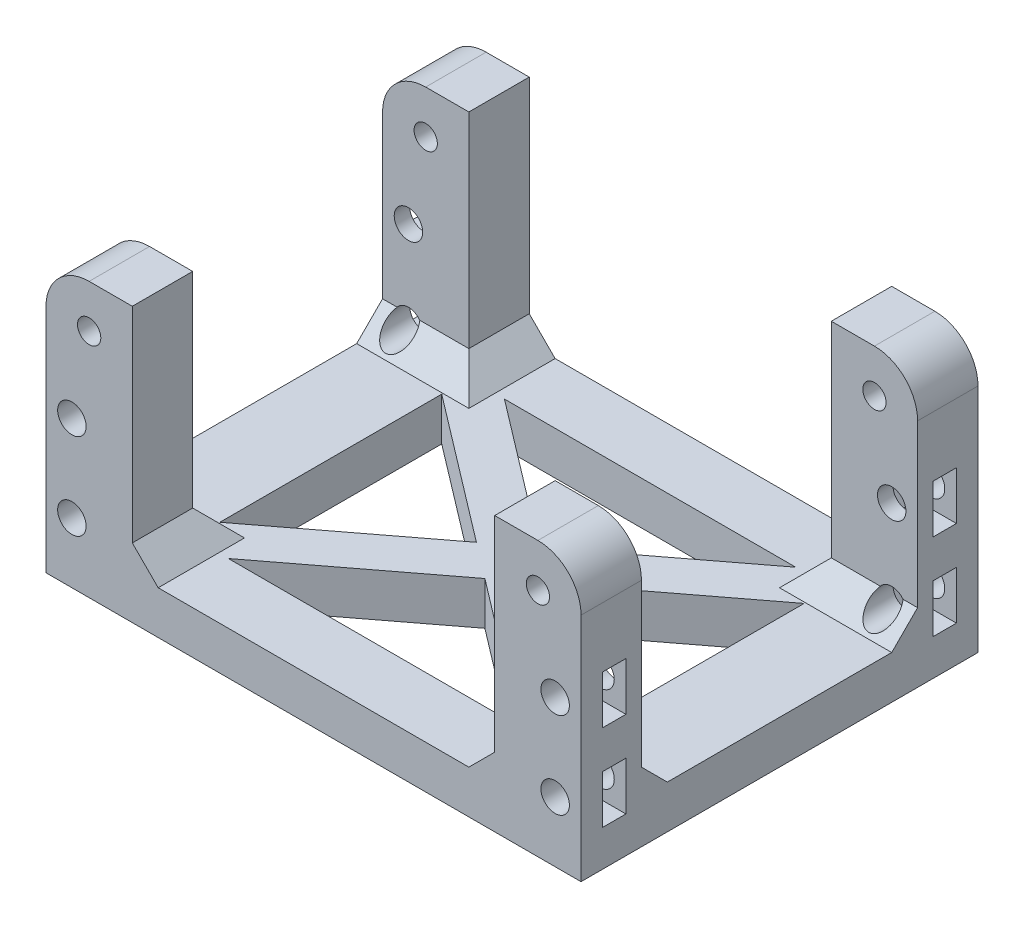
SolidWorks part; units mm, degrees
ref_plane "前视基准面" through (0, 0, 0) normal (0, 0, 1) x (1, 0, 0)
ref_plane "上视基准面" through (0, 0, 0) normal (0, 1, 0) x (1, 0, 0)
ref_plane "右视基准面" through (0, 0, 0) normal (1, 0, 0) x (0, 0, -1)
sketch "草图1" plane through (0, 0, 0) normal (0, 1, 0) x (1, 0, 0)
  line L1 (-31, -23) -> (31, -23)
  line L2 (-31, -23) -> (-31, 23)
  line L3 (-31, 23) -> (31, 23)
  line L4 (31, -23) -> (31, 23)
  line L5 (-31, -23) -> (31, 23) construction
  line L6 (-31, 23) -> (31, -23) construction
  point P0 (0, 0)
  dimension "D1" = 62
  dimension "D2" = 46
extrude "凸台-拉伸1" add sketch "草图1" along normal blind 5
sketch "草图2" plane through (0, 0, 23) normal (0, 0, 1) x (1, 0, 0)
  line L1 (-31, 5) -> (-21, 5)
  line L2 (-31, 5) -> (-31, 22)
  line L3 (-31, 22) -> (-21, 22)
  line L4 (-21, 5) -> (-21, 22)
  line L5 (31, 5) -> (21, 5)
  line L6 (31, 5) -> (31, 22)
  line L7 (31, 22) -> (21, 22)
  line L8 (21, 5) -> (21, 22)
  dimension "D1" = 17
  dimension "D2" = 10
extrude "凸台-拉伸2" add sketch "草图2" against normal blind 7
sketch "草图3" plane through (0, 0, 23) normal (0, 0, 1) x (1, 0, 0)
  line L0 (-21, 22) -> (21, 22) construction
  line L1 (0, 22) -> (0, 12) construction
  line L2 (-28, 7) -> (28, 7) construction
  line L3 (-28, 7) -> (-28, 17) construction
  line L4 (-28, 17) -> (28, 17) construction
  line L5 (28, 7) -> (28, 17) construction
  line L6 (-28, 7) -> (28, 17) construction
  line L7 (-28, 17) -> (28, 7) construction
  circle A0 centre (-28, 17) radius 1.65
  circle A1 centre (-28, 7) radius 1.65
  circle A2 centre (28, 7) radius 1.65
  circle A3 centre (28, 17) radius 1.65
  point P4 (0, 12)
  dimension "D3" = 3.3
  dimension "D1" = 10
  dimension "D2" = 56
  dimension "D4" = 10
extrude "切除-拉伸1" cut sketch "草图3" against normal blind 12
sketch "草图7" plane through (0, 22, 0) normal (0, 1, 0) x (1, 0, 0)
  line L1 (-31, -23) -> (-21, -23)
  line L2 (-31, -23) -> (-31, -16)
  line L3 (-31, -16) -> (-21, -16)
  line L4 (-21, -23) -> (-21, -16)
  line L5 (21, -23) -> (31, -23)
  line L6 (21, -23) -> (21, -16)
  line L7 (21, -16) -> (31, -16)
  line L8 (31, -23) -> (31, -16)
extrude "凸台-拉伸4" add sketch "草图7" along normal blind 9.75
sketch "草图8" plane through (0, 0, 23) normal (0, 0, 1) x (1, 0, 0)
  line L0 (-26, 31.75) -> (-26, 26.75) construction
  line L1 (-31, 31.75) -> (-21, 31.75) construction
  line L2 (26, 31.75) -> (26, 26.75) construction
  line L3 (21, 31.75) -> (31, 31.75) construction
  line L4 (-26, 26.75) -> (26, 26.75) construction
  circle A0 centre (-26, 26.75) radius 1.35
  circle A1 centre (26, 26.75) radius 1.35
  dimension "D2" = 2.7
  dimension "D1" = 5
extrude "切除-拉伸4" cut sketch "草图8" against normal up to next
ref_plane "基准面1" through (0, 0, 20.5) normal (0, 0, 1) x (1, 0, 0)
sketch "草图4" plane through (0, 0, 20.5) normal (0, 0, 1) x (1, 0, 0)
  line L0 (-29.6166, 19.8) -> (-31.2332, 19.8)
  line L1 (-24.7668, 17) -> (-26.3834, 19.8)
  line L2 (-26.3834, 19.8) -> (-29.6166, 19.8)
  line L3 (-29.6166, 19.8) -> (-31.2332, 17) construction
  line L4 (-31.2332, 17) -> (-29.6166, 14.2) construction
  line L5 (-29.6166, 14.2) -> (-26.3834, 14.2)
  line L6 (-26.3834, 14.2) -> (-24.7668, 17)
  line L7 (-24.7668, 7) -> (-26.3834, 9.8)
  line L8 (-26.3834, 9.8) -> (-29.6166, 9.8)
  line L9 (-29.6166, 9.8) -> (-31.2332, 7) construction
  line L10 (-31.2332, 7) -> (-29.6166, 4.2) construction
  line L11 (-29.6166, 4.2) -> (-26.3834, 4.2)
  line L12 (-26.3834, 4.2) -> (-24.7668, 7)
  line L13 (24.7668, 17) -> (26.3834, 14.2)
  line L14 (26.3834, 14.2) -> (29.6166, 14.2)
  line L15 (29.6166, 14.2) -> (31.2332, 17) construction
  line L16 (31.2332, 17) -> (29.6166, 19.8) construction
  line L17 (29.6166, 19.8) -> (26.3834, 19.8)
  line L18 (26.3834, 19.8) -> (24.7668, 17)
  line L19 (24.7668, 7) -> (26.3834, 4.2)
  line L20 (26.3834, 4.2) -> (29.6166, 4.2)
  line L21 (29.6166, 4.2) -> (31.2332, 7) construction
  line L22 (31.2332, 7) -> (29.6166, 9.8) construction
  line L23 (29.6166, 9.8) -> (26.3834, 9.8)
  line L24 (26.3834, 9.8) -> (24.7668, 7)
  line L25 (-31.2332, 19.8) -> (-31.2332, 17)
  line L26 (-29.6166, 14.2) -> (-31.2332, 14.2)
  line L27 (-31.2332, 14.2) -> (-31.2332, 17)
  line L28 (-29.6166, 9.8) -> (-31.2332, 9.8)
  line L29 (-31.2332, 9.8) -> (-31.2332, 7)
  line L30 (-29.6166, 4.2) -> (-31.2332, 4.2)
  line L31 (-31.2332, 4.2) -> (-31.2332, 7)
  line L32 (29.6166, 19.8) -> (31.2332, 19.8)
  line L33 (31.2332, 19.8) -> (31.2332, 17)
  line L34 (29.6166, 14.2) -> (31.2332, 14.2)
  line L35 (31.2332, 14.2) -> (31.2332, 17)
  line L36 (29.6166, 9.8) -> (31.2332, 9.8)
  line L37 (31.2332, 9.8) -> (31.2332, 7)
  line L38 (31.2332, 7) -> (31.2332, 4.2)
  line L39 (31.2332, 4.2) -> (29.6166, 4.2)
  circle A0 centre (-28, 17) radius 2.8 construction
  circle A1 centre (-28, 7) radius 2.8 construction
  circle A2 centre (28, 17) radius 2.8 construction
  circle A3 centre (28, 7) radius 2.8 construction
  dimension "D1" = 5.6
extrude "切除-拉伸2" cut sketch "草图4" against normal blind 2.7
mirror "镜向1" about plane through (0, 0, 0) normal (0, 0, 1) of "切除-拉伸4", "凸台-拉伸2", "切除-拉伸1", "切除-拉伸2", "凸台-拉伸4"
sketch "草图5" plane through (0, 31.75, 0) normal (0, 1, 0) x (1, 0, 0)
  line L1 (-21, -16) -> (21, -16)
  line L2 (-21, -16) -> (-21, 16)
  line L3 (-21, 16) -> (21, 16)
  line L4 (21, -16) -> (21, 16)
extrude "切除-拉伸3" cut sketch "草图5" against normal up to next
sketch "草图6" plane through (0, 0, 0) normal (0, 1, 0) x (1, 0, 0)
  line L0 (19.4849, -17.9886) -> (-22.5151, 14.0114)
  line L1 (19.4849, -17.9886) -> (22.5151, -14.0114)
  line L2 (-22.5151, 14.0114) -> (-19.4849, 17.9886)
  line L3 (22.5151, -14.0114) -> (-19.4849, 17.9886)
  line L4 (-21, 16) -> (21, -16) construction
  line L5 (-1.5151, -1.9886) -> (1.5151, 1.9886) construction
  line L6 (-22.5151, -14.0114) -> (19.4849, 17.9886)
  line L7 (-22.5151, -14.0114) -> (-19.4849, -17.9886)
  line L8 (19.4849, 17.9886) -> (22.5151, 14.0114)
  line L9 (-19.4849, -17.9886) -> (22.5151, 14.0114)
  line L10 (21, 16) -> (-21, -16) construction
  line L11 (-1.5151, 1.9886) -> (1.5151, -1.9886) construction
  point P1 (0, 0)
  point P2 (0, 0)
  dimension "D1" = 5
extrude "凸台-拉伸3" add sketch "草图6" along normal up to surface (5 mm away) contours L0 L6 L3 L2 | L3 L9 L8 L6 | L0 L9 L3 L6 | L7 L9 L0 L6 | L9 L0 L1 L3 region at (11.514, 0, 8.8029) region at (-11.514, 0, 8.8029) region at (0, 0, 0) region at (-11.514, 0, -8.8029) region at (11.514, 0, -8.8029) up to face at (0, 5, -19.5)
chamfer "倒角4" distance 3 angle 45 8 edges at (-21, 5, 19.5) (21, 5, 19.5) (26, 5, -16) (21, 5, -19.5) (-26, 5, -16) (-21, 5, -19.5) (-26, 5, 16) (26, 5, 16)
fillet "圆角1" radius 5 4 edges at (31, 31.75, -19.5) (31, 31.75, 19.5) (-31, 31.75, 19.5) (-31, 31.75, -19.5)
